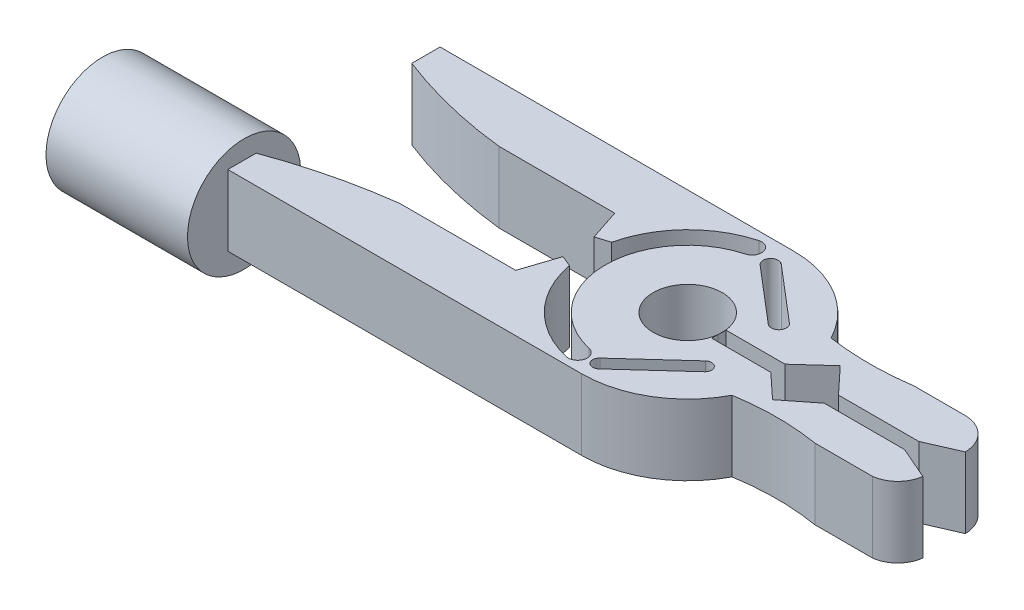
SolidWorks part; units mm, degrees
ref_plane "Front Plane" through (0, 0, 0) normal (0, 0, 1) x (1, 0, 0)
ref_plane "Top Plane" through (0, 0, 0) normal (0, 1, 0) x (1, 0, 0)
ref_plane "Right Plane" through (0, 0, 0) normal (1, 0, 0) x (0, 0, -1)
sketch "Sketch1" plane through (0, 0, 0) normal (0, 1, 0) x (1, 0, 0)
  line L0 (-7.5, 0) -> (-8.6554, 3.5)
  line L1 (5.8418, 3.5) -> (18.3418, 3.5)
  line L2 (5.8418, 3.5) -> (5.8418, -3.5)
  line L3 (5.8418, -3.5) -> (18.3418, -3.5)
  line L4 (18.3418, 3.5) -> (18.3418, -3.5)
  line L9 (0, 7.5) -> (-25, 7.5)
  line L10 (0, 7.5) -> (0, 3.5)
  line L11 (0, 3.5) -> (-25, 3.5)
  line L12 (-25, 7.5) -> (-25, 3.5)
  line L13 (0, -7.5) -> (-25, -7.5)
  line L14 (0, -7.5) -> (0, -3.5)
  line L15 (0, -3.5) -> (-25, -3.5)
  line L16 (-25, -7.5) -> (-25, -3.5)
  line L17 (-7.5, 0) -> (-8.6554, -3.5)
  line L18 (-8.6554, -3.5) -> (-6.6332, -3.5)
  circle A0 centre (0, 0) radius 7.5
  dimension "D1" = 15
  dimension "D2" = 12.5
  dimension "D3" = 7
  dimension "D4" = 25
  dimension "D5" = 25
  dimension "D6" = 4
  dimension "D7" = 4
extrude "Boss-Extrude1" add sketch "Sketch1" along normal blind 5 contours A0 L15 L16 L13 | A0 L17 L15 | A0 L11 L0 | A0 L9 L12 L11 | L10 A0 L11 | L14 A0 L3 L2 L1 L10 L11 L15 | L15 A0 L14 | L3 A0 L1 L2 | A0 L3 L4 L1 region at (-7.6745, 0, 2.4324) region at (0.2749, 0, 0) region at (-7.6745, 0, -2.4324) region at (-14.8076, 0, -5.5832) region at (-14.8076, 0, 5.5832) region at (-2.6081, 0, 5.1433) region at (-2.6081, 0, -5.1433) region at (12.777, 0, 0) region at (6.5538, 0, 0)
sketch "Sketch2" plane through (0, 5, 0) normal (0, 1, 0) x (1, 0, 0)
  line L0 (0, 5.8628) -> (3.9048, 2.5356) construction
  line L1 (0.3438, 6.2663) -> (4.2486, 2.9391)
  line L2 (-0.3438, 5.4593) -> (3.561, 2.1322)
  line L3 (3.9048, -2.6873) -> (0, -6.243) construction
  line L4 (4.2221, -3.0357) -> (0.3173, -6.5914)
  line L5 (3.5875, -2.3388) -> (-0.3173, -5.8946)
  line L6 (16.055, 0.2731) -> (18.3418, 1.2731)
  line L7 (16.055, -0.7269) -> (18.3418, -1.7269)
  line L8 (18.3418, 3.5) -> (18.3418, -3.5) construction
  line L9 (2.423, 0.2731) -> (18.3418, 0.2731)
  line L10 (2.423, 0.2731) -> (2.423, -0.7269)
  line L11 (2.423, -0.7269) -> (18.3418, -0.7269)
  line L12 (18.3418, 0.2731) -> (18.3418, -0.7269)
  line L13 (6.5996, 0.2731) -> (8.647, 2.1322)
  line L14 (8.647, 2.1322) -> (10.3824, 0.2731)
  line L17 (6.5996, 0.2731) -> (6.5996, -0.7269)
  line L18 (6.5996, -0.7269) -> (8.335, -2.3388)
  line L19 (8.335, -2.3388) -> (10.3824, -0.7269)
  line L20 (10.3824, -0.7269) -> (10.3824, 0.2731)
  line L21 (18.3418, 1.2731) -> (18.3418, 0.2731)
  line L22 (-7.5, 0) -> (-8.6554, 3.5) construction
  line L23 (-7.9363, 1.3216) -> (-7.5, 0)
  line L24 (-7.5, 0) -> (-7.8259, -0.9874)
  line L25 (-7.5, 0) -> (-8.6554, -3.5) construction
  line L26 (-7.8259, -0.9874) -> (-7.0475, -1.3099)
  line L27 (-7.9363, 1.3216) -> (-6.9862, 1.605)
  line L28 (18.3418, -0.7269) -> (18.3418, -1.7269)
  line L29 (6.6332, 3.5) -> (18.3418, 3.5) construction
  line L30 (6.6332, -3.5) -> (18.3418, -3.5) construction
  line L31 (-8.6554, 3.5) -> (-25, 3.5) construction
  line L32 (-25, 7.5) -> (-25, 3.5) construction
  line L33 (-8.6554, -3.5) -> (-25, -3.5) construction
  line L34 (-25, -7.5) -> (-25, -3.5) construction
  arc A2 (-1.713, 6.2663) -> (-1.4339, -6.336) centre (0, 0) ccw construction
  circle A7 centre (0, 0) radius 2.4384
  arc A8 (0.3438, 6.2663) -> (-0.3438, 5.4593) centre (0, 5.8628) ccw
  arc A9 (3.561, 2.1322) -> (4.2486, 2.9391) centre (3.9048, 2.5356) ccw
  arc A10 (4.2221, -3.0357) -> (3.5875, -2.3388) centre (3.9048, -2.6873) ccw
  arc A11 (-0.3173, -5.8946) -> (0.3173, -6.5914) centre (0, -6.243) ccw
  arc A12 (-1.8902, 6.9145) -> (-1.5822, -6.9914) centre (0, 0) ccw
  arc A13 (-1.5358, 5.6182) -> (-1.2856, -5.6806) centre (0, 0) ccw
  arc A14 (-1.5358, 5.6182) -> (-1.8902, 6.9145) centre (-1.713, 6.2663) ccw
  arc A15 (-1.5822, -6.9914) -> (-1.2856, -5.6806) centre (-1.4339, -6.336) ccw
  arc A16 (16.055, -3.5) -> (18.3418, -1.7269) centre (16.3119, -1.47) ccw
  arc A17 (18.3418, 1.2731) -> (16.055, 3.5) centre (16.085, 1.2432) ccw
  arc A18 (6.6332, 3.5) -> (12.4875, 3.5) centre (9.5604, 23.3279) ccw
  arc A19 (6.6332, -3.5) -> (12.4875, -3.5) centre (9.5604, -21.0533) cw
  arc A20 (6.6332, 3.5) -> (0, 7.5) centre (0, 0) ccw construction
  arc A21 (-16.8277, 3.5) -> (-25, 5.5) centre (-13.358, 35.3742) cw
  arc A22 (-16.8277, -3.5) -> (-25, -5.5) centre (-12.28, -39.7792) ccw
  point P5 (-6.4947, -0.1438)
  point P14 (1.9524, 4.1992)
  point P21 (1.9524, -4.4651)
  line M28 (6.6332, -3.5) -> (18.3418, -3.5)
  line M29 (18.3418, -3.5) -> (18.3418, 3.5)
  line M30 (18.3418, 3.5) -> (6.6332, 3.5)
  line M33 (-25, 7.5) -> (-25, 3.5)
  line M34 (-25, 3.5) -> (-8.6554, 3.5)
  line M35 (-8.6554, 3.5) -> (-7.5, 0)
  line M36 (-7.5, 0) -> (-8.6554, -3.5)
  line M37 (-8.6554, -3.5) -> (-25, -3.5)
  line M38 (-25, -3.5) -> (-25, -7.5)
  dimension "D1" = 1
  dimension "D2" = 1
  dimension "D3" = 1
extrude "Cut-Extrude1" cut sketch "Sketch2" against normal through all both and the other way through all contours A22 M37 M38 | A21 M34 M33 | L10 A7 | A7 L10 L11 L17 L9 | L11 L20 L9 L17 | L14 L13 L9 | L20 L11 L9 M29 | L6 L9 M29 | L11 L7 M29 | A16 M28 M29 | A12 A15 A13 A14 | L2 A9 L1 A8 | L5 A11 L4 A10 | L18 L19 L11 | A12 L27 L26 M35 M36 | A17 M29 M30 | A18 M30 | A19 M28 region at (1.9524, 5, -4.1992) region at (1.9524, 5, 4.4651) region at (9.5604, 5, -3.414) region at (17.8379, 5, -2.9961) region at (9.5604, 5, 3.403) region at (17.9023, 5, 3.0604) region at (14.3621, 5, 0.2269) region at (17.5796, 5, -0.6065) region at (8.491, 5, 0.2269) region at (8.543, 5, -0.8928) region at (4.5141, 5, 0.2272) region at (8.439, 5, 1.2642) region at (17.5796, 5, 1.0602) region at (-0.0007, 5, 0) region at (-7.41, 5, -0.237) region at (-22.5439, 5, 4.1188) region at (-22.59, 5, -4.1136) region at (-5.0608, 5, -4.8574)
sketch "Sketch3" plane through (-25, 0, 0) normal (-1, 0, 0) x (0, 0, 1)
  circle A0 centre (6.3503, 2.313) radius 4
  dimension "D1" = 8
extrude "Boss-Extrude2" add sketch "Sketch3" along normal blind 10
